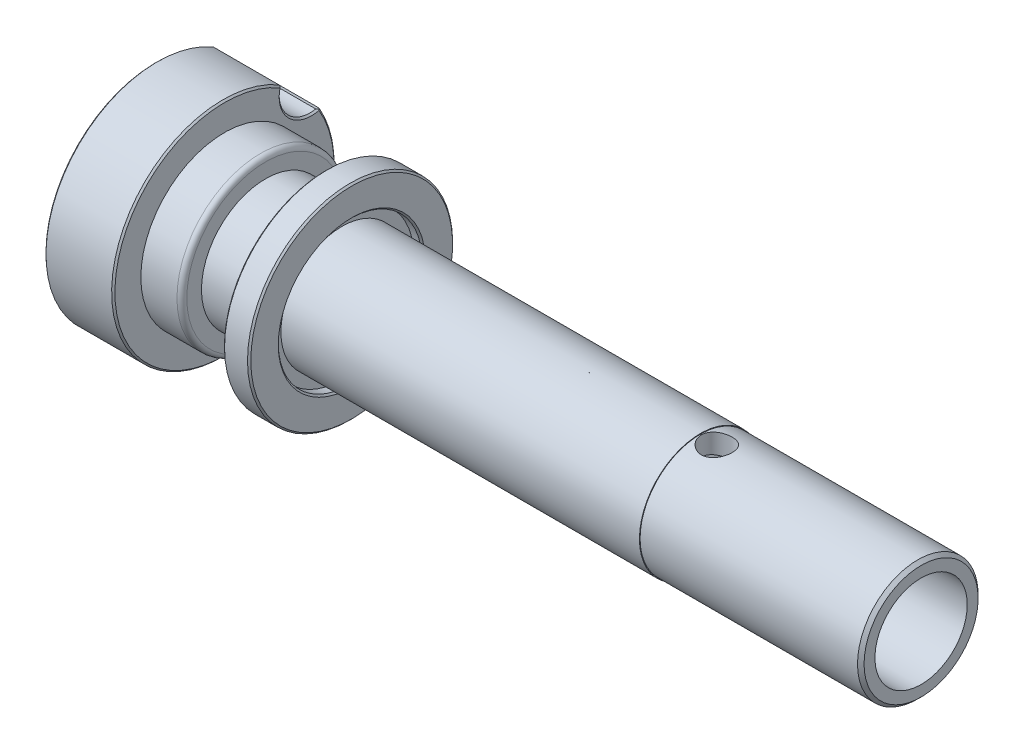
SolidWorks part; units mm, degrees
ref_plane "Front Plane" through (0, 0, 0) normal (0, 0, 1) x (1, 0, 0)
ref_plane "Top Plane" through (0, 0, 0) normal (0, 1, 0) x (1, 0, 0)
ref_plane "Right Plane" through (0, 0, 0) normal (1, 0, 0) x (0, 0, -1)
sketch "Sketch1" plane through (0, 0, 0) normal (0, 1, 0) x (1, 0, 0)
  line L0 (0, 0) -> (169.0742, 0) construction
  line L1 (0, 6.35) -> (118.491, 6.35)
  line L2 (118.491, 6.35) -> (118.491, 9.3345)
  line L3 (118.491, 9.3345) -> (84.328, 9.3345)
  line L4 (84.328, 9.3345) -> (84.328, 9.4361)
  line L5 (84.328, 9.4361) -> (30.353, 9.4361)
  line L6 (30.353, 9.4361) -> (30.353, 15.875)
  line L7 (30.353, 15.875) -> (26.289, 15.875)
  line L8 (26.289, 15.875) -> (26.289, 9.9219)
  line L9 (26.289, 9.9219) -> (17.018, 9.9219)
  line L10 (17.018, 9.9219) -> (17.018, 12.954)
  line L11 (17.018, 12.954) -> (10.668, 12.954)
  line L12 (10.668, 12.954) -> (10.668, 17.2212)
  line L13 (10.668, 17.2212) -> (0, 17.2212)
  line L14 (0, 17.2212) -> (0, 6.35)
  point P5 (13.843, 12.954)
  dimension "D1" = 18.669
  dimension "D2" = 18.8722
  dimension "D3" = 31.75
  dimension "D4" = 19.8438
  dimension "D5" = 25.908
  dimension "D6" = 34.4424
  dimension "D7" = 34.163
  dimension "D8" = 53.975
  dimension "D9" = 4.064
  dimension "D10" = 9.271
  dimension "D11" = 6.35
  dimension "D12" = 10.668
  dimension "D13" = 12.7
revolve "Revolve1" add sketch "Sketch1" angle 360 about L0
chamfer "Chamfer1" distance 0.508 angle 45 1 edges at (118.491, 0, 9.3345)
chamfer "Chamfer2" distance 0.254 angle 45 4 edges at (10.668, 0, 17.2212) (0, 0, 17.2212) (30.353, 0, 15.875) (26.289, 0, 15.875)
fillet "Fillet1" radius 0.762 1 edges at (17.018, 0, 12.954)
sketch "Sketch2" plane through (0, 0, 0) normal (-1, 0, 0) x (0, 0, 1)
  point P0 (0, 15.0813)
  point P2 (15.0812, 0)
  point P4 (0, -15.0812)
  point P6 (-15.0813, 0)
hole_wizard "#6-32 Tapped Hole1" positions "Sketch2" profile "Sketch3" tap size "#6-32" standard "ANSI Inch"
sketch "Sketch3" plane through (0, 15.0813, 0) normal (0, 1, 0) x (0, 0, 1)
  line L0 (0, 0) -> (0, 8.89)
  line L1 (0, 8.89) -> (1.3525, 8.0773)
  line L2 (1.3525, 8.0773) -> (1.3525, 0.5525)
  line L3 (1.3525, 0.5525) -> (1.905, 0)
  line L5 (1.905, 0) -> (0, 0)
  line L6 (-1.3525, 0.5524) -> (-1.905, 0) construction
  line L10 (0, 8.89) -> (-1.3526, 8.0773) construction
  line L11 (0, -6.35) -> (0, 107.95) construction
  dimension "Tap Drill Dia." = 2.7051
  dimension "Tap Drill Depth" = 8.89
  dimension "Near C'Sink Dia." = 3.81
  dimension "Near C'Sink Angle" = 90
  dimension "Drill Angle" = 118
cosmetic thread "Hole Thread5" parameters "D1"=8.0975, "D2"=3.5052
cosmetic thread "Hole Thread6" parameters "D1"=8.0975, "D2"=3.5052
cosmetic thread "Hole Thread7" parameters "D1"=8.0975, "D2"=3.5052
cosmetic thread "Hole Thread8" parameters "D1"=8.0975, "D2"=3.5052
sketch "Sketch4" plane through (0, 0, 0) normal (-1, 0, 0) x (0, 0, 1)
  line L0 (0, 18.1571) -> (0, 0) construction
  line L1 (0, 0) -> (-15.8632, 15.8632) construction
  circle A0 centre (-13.4704, 13.4704) radius 4.7625
  dimension "D2" = 19.05
  dimension "D1" = 45
extrude "Cut-Extrude1" cut sketch "Sketch4" against normal up to next
chamfer "Chamfer3" distance 0.254 angle 45 4 edges at (10.668, 10.1028, -10.1028) (0, 10.1028, -10.1028) (5.334, 14.7529, -8.8838) (5.334, 8.8838, -14.7529)
sketch "Sketch5" plane through (0, 0, 0) normal (-1, 0, 0) x (0, 0, 1)
  circle A0 centre (0, 0) radius 7.9375
extrude "Cut-Extrude2" cut sketch "Sketch5" against normal blind 9.7841
sketch "Sketch6" plane through (0, 0, 0) normal (-1, 0, 0) x (0, 0, 1)
  circle A0 centre (0, 0) radius 11.1125
extrude "Cut-Extrude3" cut sketch "Sketch6" against normal blind 1.5875
chamfer "Chamfer4" distance 0.508 angle 45 1 edges at (1.5875, 0, 7.9375)
sketch "Sketch7" plane through (0, 0, 0) normal (0, 1, 0) x (1, 0, 0)
  line L0 (84.328, -9.4361) -> (84.328, 9.4361) construction
  circle A0 centre (86.868, 0) radius 2.3813
  dimension "D1" = 2.54
extrude "Cut-Extrude4" cut sketch "Sketch7" against normal through all both and the other way through all
sketch "Sketch8" plane through (30.353, 0, 0) normal (1, 0, 0) x (0, 0, -1)
  circle A0 centre (0, 0) radius 9.4361 construction
  circle A1 centre (0, 0) radius 9.4361
  circle A2 centre (0, 0) radius 11.1125
  dimension "D1" = 22.225
extrude "Cut-Extrude5" cut sketch "Sketch8" against normal blind 1.524 and the other way through all
chamfer "Chamfer5" distance 0.254 angle 45 1 edges at (30.353, 0, 11.1125)
sketch "Sketch9" plane through (118.491, 0, 0) normal (1, 0, 0) x (0, 0, -1)
  circle A0 centre (0, 0) radius 7.1438
  dimension "D1" = 14.2875
extrude "Cut-Extrude6" cut sketch "Sketch9" against normal blind 12.7
sketch "Sketch10" plane through (9.7841, 0, 0) normal (-1, 0, 0) x (0, 0, 1)
  circle A0 centre (0, 0) radius 7.1438
  dimension "D1" = 14.2875
extrude "Cut-Extrude7" cut sketch "Sketch10" against normal offset from surface (12.7 mm away) 96.0069 up to face at (118.491, 0, -7.1438)
